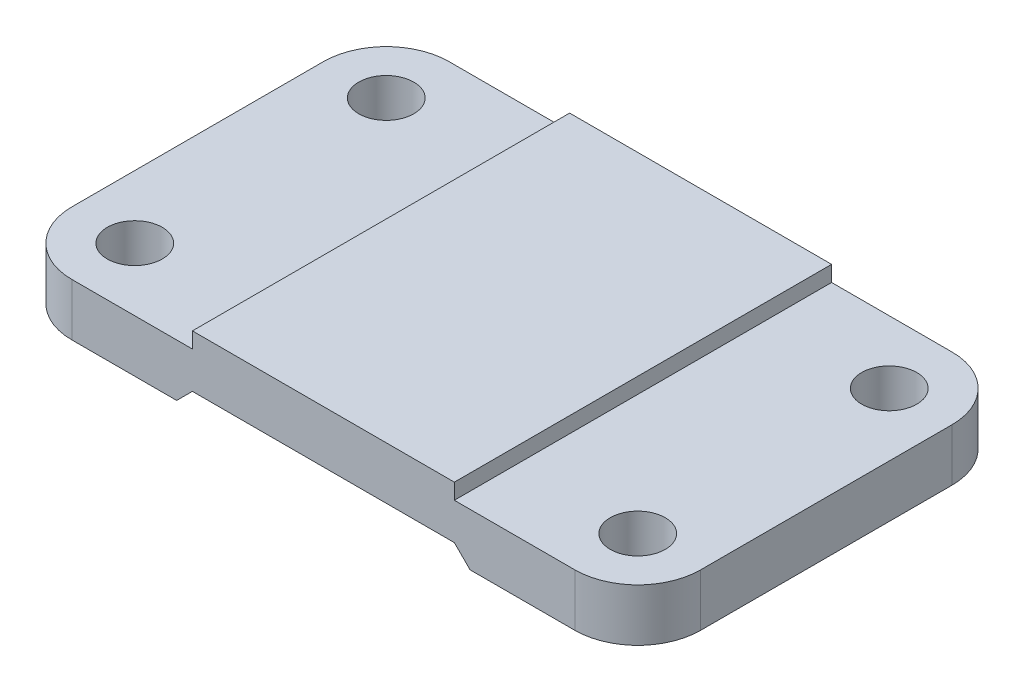
SolidWorks part; units mm, degrees
ref_plane "Front Plane" through (0, 0, 0) normal (0, 0, 1) x (1, 0, 0)
ref_plane "Top Plane" through (0, 0, 0) normal (0, 1, 0) x (1, 0, 0)
ref_plane "Right Plane" through (0, 0, 0) normal (1, 0, 0) x (0, 0, -1)
sketch "Sketch1" plane through (0, 0, 0) normal (0, 0, 1) x (1, 0, 0)
  line L0 (-25, 5) -> (25, 5)
  line L1 (60, 5) -> (-60, 5)
  line L2 (60, 5) -> (60, -5)
  line L3 (60, -5) -> (-60, -5)
  line L4 (-60, 5) -> (-60, -5)
  line L5 (0, -5) -> (0, 5) construction
  line L6 (-28, -5) -> (28, -5)
  line L7 (-28, -5) -> (-25, -2)
  line L8 (0, 5) -> (-25, 5)
  line L10 (0, 8) -> (-25, 8)
  line L11 (-25, 5) -> (-25, 8)
  line L12 (0, 5) -> (25, 5)
  line L14 (0, 8) -> (25, 8)
  line L15 (25, 5) -> (25, 8)
  line L16 (-25, -2) -> (25, -2)
  line L17 (28, -5) -> (25, -2)
  line L18 (25, 8) -> (-25, 8)
  point P0 (0, 0)
  point P15 (0, -2)
  dimension "D1" = 10
  dimension "D2" = 120
  dimension "D3" = 25
  dimension "D4" = 3
  dimension "D5" = 25
  dimension "D6" = 3
  dimension "D7" = 28
  dimension "D8" = 45
extrude "Boss-Extrude1" add sketch "Sketch1" along normal blind 36 and the other way blind 36 contours L1 L15 L14 L10 L11 L0 | L16 L5 L0 L1 L4 L3 L7 | L5 L16 L17 L3 L2 L1 region at (0, 6.5, 0) region at (-32.5562, 0.5389, 0) region at (32.5562, 0.5389, 0)
fillet "Fillet1" radius 12 4 edges at (-60, 0, -36) (-60, 0, 36) (60, 0, -36) (60, 0, 36)
hole_wizard "M12x1.5 Tapped Hole1" positions "Sketch4" profile "Sketch5" tap size "M12x1.5" standard "ISO" end condition through all
sketch "Sketch4" plane through (0, 5, 0) normal (0, 1, 0) x (1, 0, 0)
  point P0 (-48, -24)
  point P3 (-48, 24)
  point P6 (48, 24)
  point P9 (48, -24)
sketch "Sketch5" plane through (-48, 5, 24) normal (1, 0, 0) x (0, 0, 1)
  line L0 (0, 0) -> (0, 10)
  line L1 (0, 10) -> (5.25, 10)
  line L2 (5.25, 10) -> (5.25, 0)
  line L5 (5.25, 0) -> (0, 0)
  line L11 (0, -6.35) -> (0, 107.95) construction
  dimension "Thru Tap Drill Dia." = 10.5
  dimension "Thru Tap Drill Depth" = 10
cosmetic thread "Hole Thread1" parameters "D2"=12
cosmetic thread "Hole Thread2" parameters "D2"=12
cosmetic thread "Hole Thread3" parameters "D2"=12
cosmetic thread "Hole Thread4" parameters "D2"=12
